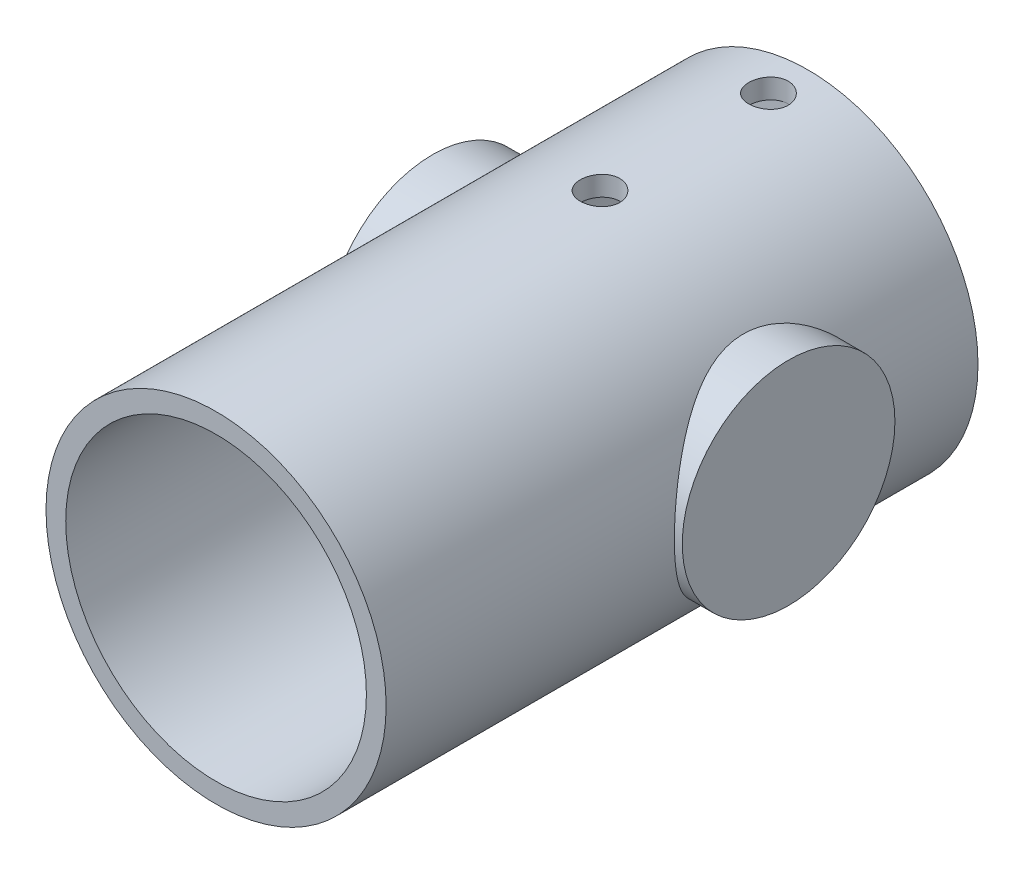
SolidWorks part; units mm, degrees
ref_plane "Front Plane" through (0, 0, 0) normal (0, 0, 1) x (1, 0, 0)
ref_plane "Top Plane" through (0, 0, 0) normal (0, 1, 0) x (1, 0, 0)
ref_plane "Right Plane" through (0, 0, 0) normal (1, 0, 0) x (0, 0, -1)
sketch "Sketch1" plane through (0, 0, 0) normal (0, 0, 1) x (1, 0, 0)
  circle A1 centre (0, 0) radius 43.1
  dimension "D1" = 86.2
extrude "Boss-Extrude1" add sketch "Sketch1" along normal blind 150
ref_plane "Plane1" through (0, 43.1, 0) normal (0, 1, 0) x (1, 0, 0)
sketch "Sketch6" plane through (0, 43.1, 0) normal (0, 1, 0) x (1, 0, 0)
  circle A0 centre (0, -10) radius 5
  circle A1 centre (0, -52.7) radius 5
  dimension "D2" = 10
  dimension "D1" = 10
  dimension "D3" = 42.7
extrude "Cut-Extrude3" cut sketch "Sketch6" against normal through all
ref_plane "Plane2" through (45.1, 0, 0) normal (1, 0, 0) x (0, 0, -1)
sketch "Sketch8" plane through (45.1, 0, 0) normal (1, 0, 0) x (0, 0, -1)
  circle A0 centre (-50, 0) radius 26.95
  point P2 (0, 0)
  point P4 (-46.4005, 0)
  dimension "D1" = 53.9
  dimension "D2" = 50
extrude "Boss-Extrude2" add sketch "Sketch8" against normal blind 20
mirror "Mirror1" about plane through (0, 0, 0) normal (1, 0, 0) of "Boss-Extrude2"
sketch "Sketch5" plane through (0, 0, 150) normal (0, 0, 1) x (1, 0, 0)
  circle A0 centre (0, 0) radius 31.75
  dimension "D1" = 63.5
sketch "Sketch2" plane through (0, 0, 150) normal (0, 0, 1) x (1, 0, 0)
  circle A0 centre (0, 0) radius 38.1
  dimension "D1" = 76.2
extrude "Cut-Extrude4" cut sketch "Sketch5" against normal through all
extrude "Cut-Extrude5" cut sketch "Sketch2" against normal blind 145
